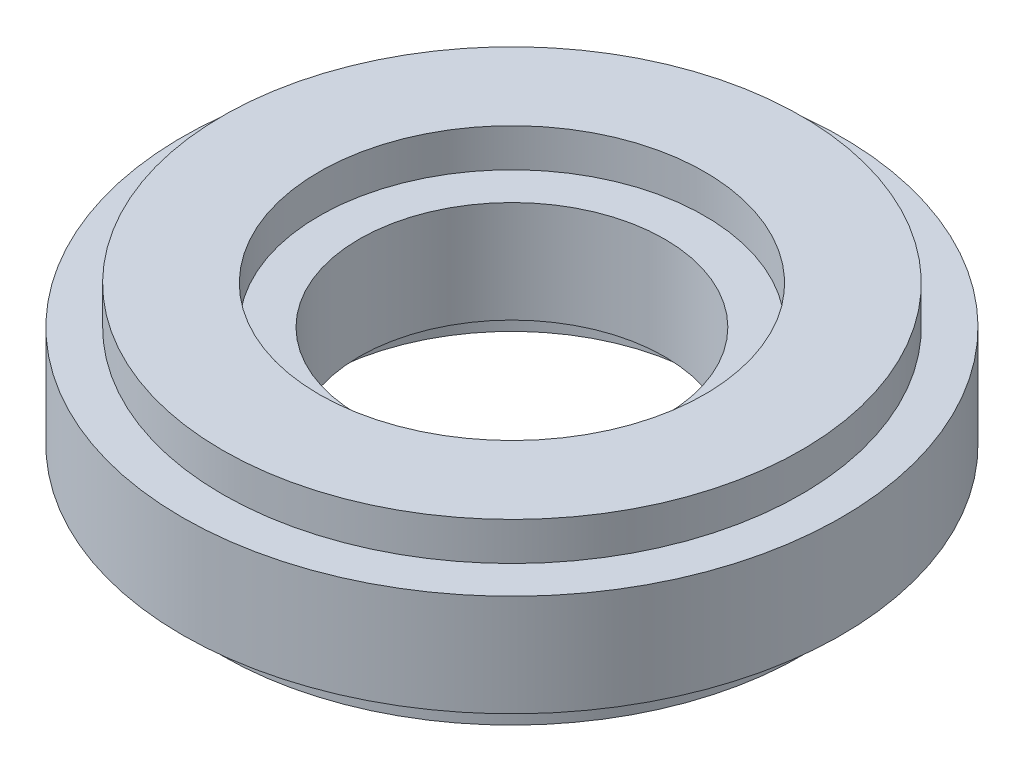
SolidWorks part; units mm, degrees
ref_plane "Front Plane" through (0, 0, 0) normal (0, 0, 1) x (1, 0, 0)
ref_plane "Top Plane" through (0, 0, 0) normal (0, 1, 0) x (1, 0, 0)
ref_plane "Right Plane" through (0, 0, 0) normal (1, 0, 0) x (0, 0, -1)
ref_axis "Axis1" through (0, 0, 0) along (0, 1, 0)
sketch "Sketch1" plane through (0, 0, 0) normal (0, 0, 1) x (1, 0, 0)
  line L0 (0, 0) -> (0, -15310.4622) construction
  line L2 (-25.9, 4) -> (-12, 4)
  line L3 (-25.9, 4) -> (-25.9, -4)
  line L4 (-25.9, -4) -> (-12, -4)
  line L5 (-12, 4) -> (-12, -4)
  point P7 (-12, 0)
  dimension "D1" = 24
  dimension "D2" = 51.8
  dimension "D3" = 8
revolve "Revolve1" add sketch "Sketch1" angle 360 about L0
sketch "Sketch2" plane through (0, 0, 0) normal (0, 0, 1) x (1, 0, 0)
  line L1 (-22.7479, 7) -> (-15.1521, 7)
  line L2 (-22.7479, 7) -> (-22.7479, -7)
  line L3 (-22.7479, -7) -> (-15.1521, -7)
  line L4 (-15.1521, 7) -> (-15.1521, -7)
  line L5 (-18.95, 4) -> (-18.95, 7) construction
  line L6 (-25.9, 4) -> (-12, 4) construction
  line L7 (-25.9, -4) -> (-12, -4) construction
  dimension "D1" = 3
  dimension "D2" = 3
revolve "Revolve2" add sketch "Sketch2" angle 360 about L0
